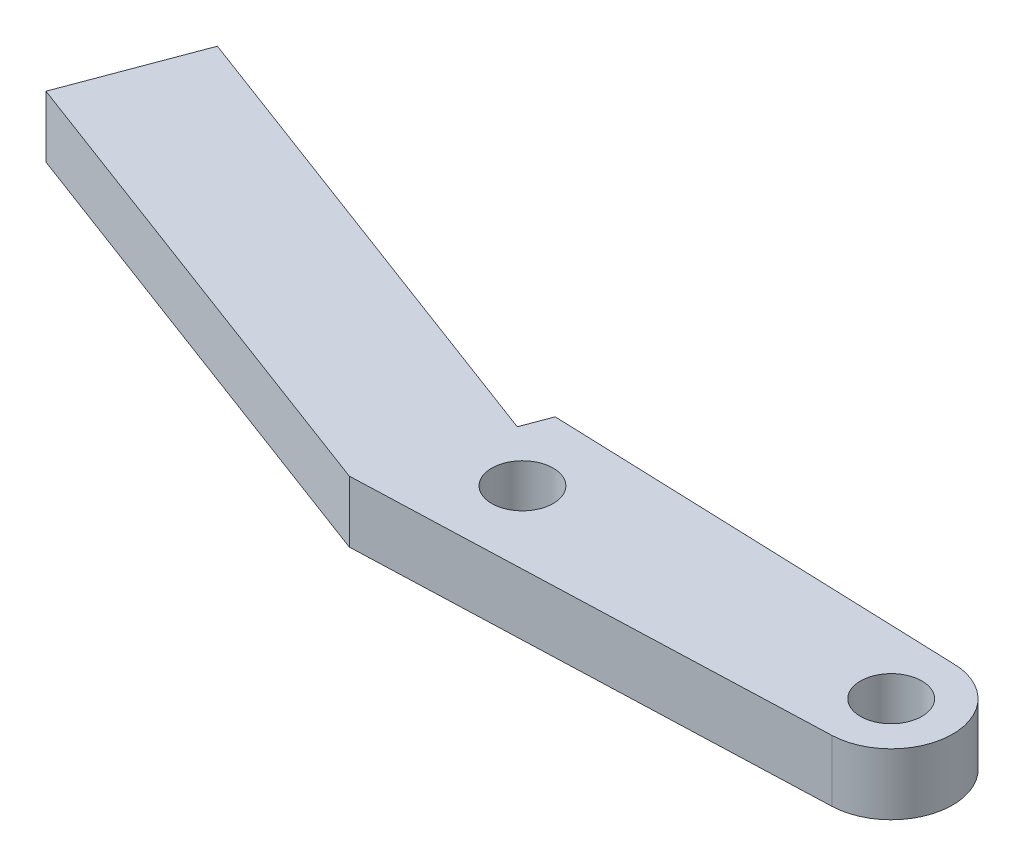
SolidWorks part; units mm, degrees
ref_plane "Alzado" through (0, 0, 0) normal (0, 0, 1) x (1, 0, 0)
ref_plane "Planta" through (0, 0, 0) normal (0, 1, 0) x (1, 0, 0)
ref_plane "Vista lateral" through (0, 0, 0) normal (1, 0, 0) x (0, 0, -1)
sketch "Croquis1" plane through (0, 0, 0) normal (0, 1, 0) x (1, 0, 0)
  line L0 (-5.2369, 0.7539) -> (18.439, -8.1161)
  line L1 (18.439, -8.1161) -> (41.1842, -7.2972)
  line L2 (-5.2369, 0.7539) -> (-2.9565, 6.8408)
  line L3 (-2.9565, 6.8408) -> (20.4545, -1.93)
  line L4 (20.4545, -1.93) -> (20.959, -0.5832)
  line L5 (20.959, -0.5832) -> (41.0763, -1.2992)
  line L6 (23.0763, -4.2992) -> (41.0763, -4.2992) construction
  line L7 (22.9451, -0.6539) -> (23.2075, -7.9444) construction
  circle A0 centre (41.0763, -4.2992) radius 1.5
  circle A1 centre (23.0763, -4.2992) radius 1.5
  arc A2 (41.1842, -7.2972) -> (41.0763, -1.2992) centre (41.0763, -4.2992) ccw
  dimension "D1" = 3
  dimension "D3" = 6
  dimension "D2" = 18
  dimension "D4" = 6.5
  dimension "D5" = 25
  dimension "D6" = 4.1
  dimension "D7" = 22.76
  dimension "D8" = 20.13
  dimension "D9" = 108.5
  dimension "D10" = 157.4
extrude "Saliente-Extruir1" add sketch "Croquis1" along normal blind 3
